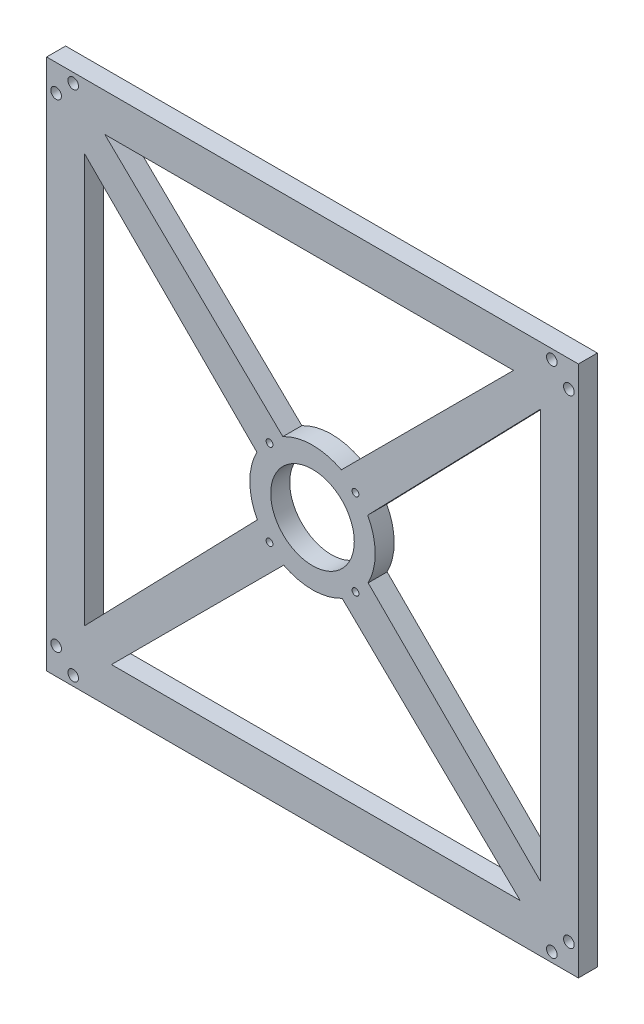
SolidWorks part; units mm, degrees
ref_plane "Front Plane" through (0, 0, 0) normal (0, 0, 1) x (1, 0, 0)
ref_plane "Top Plane" through (0, 0, 0) normal (0, 1, 0) x (1, 0, 0)
ref_plane "Right Plane" through (0, 0, 0) normal (1, 0, 0) x (0, 0, -1)
sketch "Sketch3" plane through (0, 0, 0) normal (0, 0, 1) x (1, 0, 0)
  line L1 (-70, 70) -> (70, 70)
  line L2 (-70, 70) -> (-70, -70)
  line L3 (-70, -70) -> (70, -70)
  line L4 (70, 70) -> (70, -70)
  line L5 (0, -70) -> (0, 70) construction
  line L6 (-70, 0) -> (70, 0) construction
  point P0 (0, 0)
  dimension "D1" = 140
  dimension "D2" = 140
extrude "Boss-Extrude1" add sketch "Sketch3" along normal blind 5
sketch "Sketch4" plane through (0, 0, 5) normal (0, 0, 1) x (1, 0, 0)
  line L0 (0, 0) -> (-70, 70) construction
  line L1 (0, 0) -> (70, 70) construction
  line L2 (-60, 60) -> (60, 60) construction
  line L3 (70, 70) -> (-70, 70) construction
  line L4 (-65, 70) -> (3.5355, 3.5355) construction
  line L5 (-3.5355, 3.5355) -> (52.9289, 60) construction
  line L6 (7.5831, 14.6542) -> (52.9289, 60)
  line L7 (-7.8076, 14.5359) -> (-54.6884, 60)
  line L8 (-54.6884, 60) -> (52.9289, 60)
  circle A0 centre (0, 0) radius 16.5 construction
  arc A1 (-7.8076, 14.5359) -> (7.5831, 14.6542) centre (0, 0) cw
  dimension "D1" = 33
  dimension "D2" = 10
  dimension "D3" = 10
  dimension "D4" = 5
  dimension "D5" = 5
  dimension "D6" = 5
extrude "Cut-Extrude1" cut sketch "Sketch4" against normal blind 5
pattern_circular "CirPattern1" count 4 over 360 about axis through (0, 0, 5) along (0, 0, -1) of "Cut-Extrude1"
sketch "Sketch7" plane through (0, 0, 5) normal (0, 0, 1) x (1, 0, 0)
  circle A0 centre (0, 0) radius 11
  dimension "D1" = 22
extrude "Cut-Extrude2" cut sketch "Sketch7" against normal up to next
sketch "Sketch8" plane through (0, 0, 5) normal (0, 0, 1) x (1, 0, 0)
  line L0 (0, 0) -> (70, -70) construction
  circle A0 centre (0, 0) radius 16 construction
  point P3 (11.3137, -11.3137)
  dimension "D1" = 32
hole_wizard "Ø1.8 (1.8) Diameter Hole1" positions "3DSketch3" profile "Sketch9" hole size "Ø1.8" standard "ANSI Metric"
sketch3d "3DSketch3"
  point P0 (11.3137, -11.3137, 5)
sketch "Sketch9" plane through (11.3137, -11.3137, 5) normal (1, 0, 0) x (0, -1, 0)
  line L0 (0, 0) -> (0, 6.5408)
  line L1 (0, 6.5408) -> (0.9, 6)
  line L2 (0.9, 6) -> (0.9, 0)
  line L5 (0.9, 0) -> (0, 0)
  line L10 (0, 6.5408) -> (-0.9, 6) construction
  line L11 (0, -6.35) -> (0, 107.95) construction
  dimension "Hole Dia." = 1.8
  dimension "Hole Depth" = 6
  dimension "Drill Angle" = 118
pattern_circular "CirPattern2" count 4 over 360 about axis through (0, 0, 0) along (0, 0, 1) of "Ø1.8 (1.8) Diameter Hole1"
hole_wizard "Ø3.0mm Dowel Hole1" positions "3DSketch4" profile "Sketch10" hole size "Ø3.0" standard "ANSI Metric"
sketch3d "3DSketch4"
  line L0 (70, -70, 0) -> (70, 70, 0) construction
  point P0 (67.5, -63, 0)
  dimension "D1" = 63
  dimension "D2" = 2.5
sketch "Sketch10" plane through (67.5, -63, 0) normal (1, 0, 0) x (0, 1, 0)
  line L0 (0, 0) -> (0, 10.8412)
  line L1 (0, 10.8412) -> (1.4, 10)
  line L2 (1.4, 10) -> (1.4, 0)
  line L5 (1.4, 0) -> (0, 0)
  line L10 (0, 10.8412) -> (-1.4, 10) construction
  line L11 (0, -6.35) -> (0, 107.95) construction
  dimension "Hole Dia." = 2.8
  dimension "Hole Depth" = 10
  dimension "Drill Angle" = 118
hole_wizard "Ø3.0mm Dowel Hole2" positions "3DSketch5" profile "Sketch11" hole size "Ø3.0" standard "ANSI Metric"
sketch3d "3DSketch5"
  line L0 (-70, -70, 5) -> (70, -70, 5) construction
  point P0 (63, -67.5, 5)
  dimension "D1" = 63
  dimension "D2" = 2.5
sketch "Sketch11" plane through (63, -67.5, 5) normal (1, 0, 0) x (0, -1, 0)
  line L0 (0, 0) -> (0, 10.8412)
  line L1 (0, 10.8412) -> (1.4, 10)
  line L2 (1.4, 10) -> (1.4, 0)
  line L5 (1.4, 0) -> (0, 0)
  line L10 (0, 10.8412) -> (-1.4, 10) construction
  line L11 (0, -6.35) -> (0, 107.95) construction
  dimension "Hole Dia." = 2.8
  dimension "Hole Depth" = 10
  dimension "Drill Angle" = 118
ref_axis "Axis1" through (0, 0, 5.25) along (0, 0, -1)
pattern_circular "CirPattern3" count 4 over 360 about axis through (0, 0, 5.25) along (0, 0, -1) of "Ø3.0mm Dowel Hole1", "Ø3.0mm Dowel Hole2"
